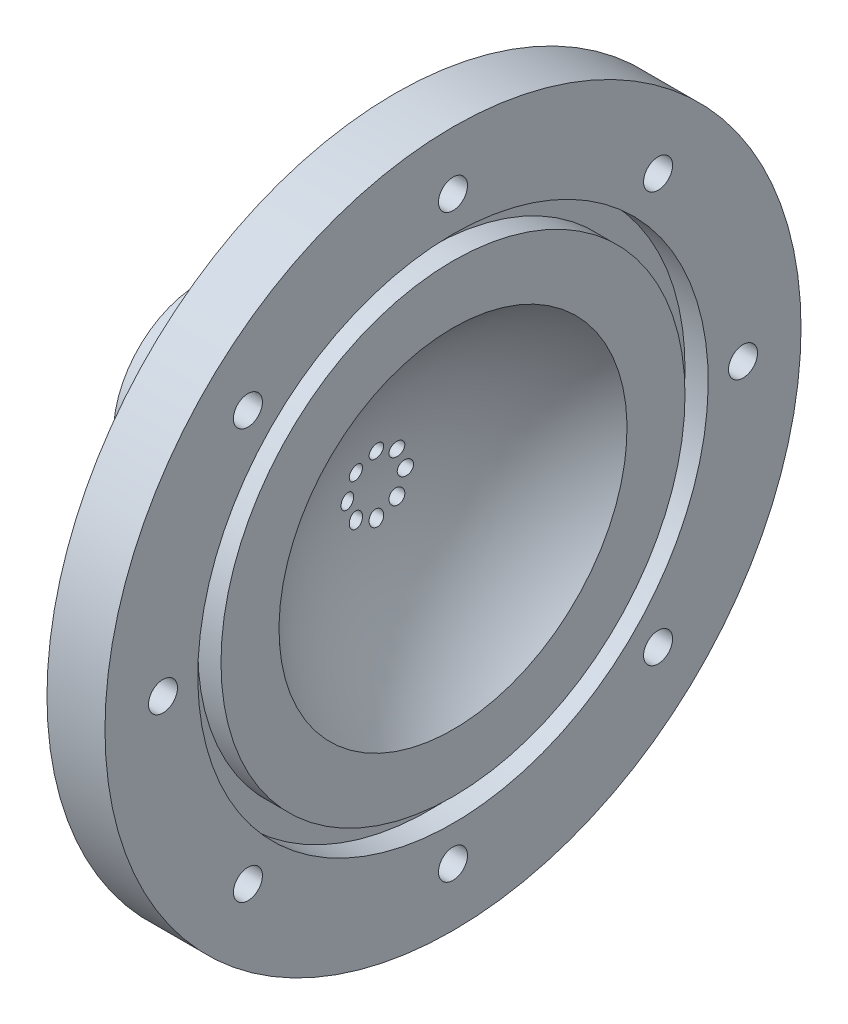
SolidWorks part; units mm, degrees
ref_plane "Front Plane" through (0, 0, 0) normal (0, 0, 1) x (1, 0, 0)
ref_plane "Top Plane" through (0, 0, 0) normal (0, 1, 0) x (1, 0, 0)
ref_plane "Right Plane" through (0, 0, 0) normal (1, 0, 0) x (0, 0, -1)
ref_axis "Axis1" through (-98.515, 0, 0) along (1, 0, 0)
sketch "Sketch1" plane through (0, 0, 0) normal (0, 0, 1) x (1, 0, 0)
  line L0 (0, 38.1) -> (0, 27.94)
  line L1 (-8.5995, 0) -> (-27.6495, 0)
  line L2 (-27.6495, 0) -> (-27.6495, 9.525)
  line L3 (-27.6495, 9.525) -> (-13.487, 9.525)
  line L4 (-6.35, 21.7282) -> (-6.35, 38.1)
  line L5 (-6.35, 38.1) -> (0, 38.1)
  line L6 (0, 19.05) -> (0, 25.4)
  line L7 (0, 25.4) -> (-2.54, 25.4)
  line L8 (-2.54, 25.4) -> (-2.54, 27.94)
  line L9 (-2.54, 27.94) -> (0, 27.94)
  line L10 (-98.515, 0) -> (79.465, 0) construction
  arc A0 (0, 19.05) -> (-8.5995, 0) centre (16.8005, 0) ccw
  arc A1 (-6.35, 21.7282) -> (-13.487, 9.525) centre (16.8005, 0) ccw
  point P1 (-6.35, 19.3161)
  point P6 (-6.35, 19.8543)
  point P8 (-1.27, 25.4)
  point P15 (-6.35, 18.6582)
  point P19 (-10.5795, 12.7433)
  dimension "D2" = 25.4
  dimension "D8" = 31.75
  dimension "D3" = 6.35
  dimension "D4" = 9.525
  dimension "D5" = 2.54
  dimension "D6" = 2.54
  dimension "D7" = 25.4
  dimension "D9" = 19.05
  dimension "D10" = 19.05
  dimension "D11" = 38.1
revolve "Revolve1" add sketch "Sketch1" angle 360 about L1
hole_wizard "1/4 NPT Tapped Hole1" positions "Sketch4" profile "Sketch5" size "1/4" standard "ANSI Inch"
sketch "Sketch4" plane through (-27.6495, 0, 0) normal (-1, 0, 0) x (0, 0, 1)
  point P0 (0, 0)
cosmetic thread "Hole Thread1" parameters "D1"=9.906, "D2"=13.7086
sketch "Sketch5" plane through (-27.6495, 0, 0) normal (0, 1, 0) x (0, 0, 1)
  line L0 (0, 0) -> (0, 16.0423)
  line L1 (5.5626, 12.7) -> (0, 16.0423)
  line L2 (-5.5626, 12.7) -> (0, 16.0423) construction
  line L3 (5.5626, 12.7) -> (5.5626, 9.906)
  line L4 (5.5626, 9.906) -> (5.9437, 9.906)
  line L5 (5.9437, 9.906) -> (6.2403, 0)
  line L6 (-5.9437, 9.906) -> (-6.2403, 0) construction
  line L7 (6.2403, 0) -> (0, 0)
  line L8 (0, -6.35) -> (0, 107.95) construction
  line L11 (-5.5626, 9.906) -> (-5.9437, 9.906) construction
  dimension "Tap Drill Dia." = 11.1252
  dimension "Tap Drill Depth" = 12.7
  dimension "Thread Dia." = 12.4806
  dimension "Thread Angle" = 3.43
  dimension "Thread Depth" = 9.906
  dimension "Drill Angle" = 118
hole_wizard "1/16 (0.0625) Diameter Hole1" positions "Sketch6" profile "Sketch7" hole size "1/16" standard "ANSI Inch" end condition through all
sketch "Sketch6" plane through (0, 0, 0) normal (1, 0, 0) x (0, 0, -1)
  point P0 (0, 3.175)
  dimension "D1" = 3.175
sketch "Sketch7" plane through (0, 3.175, 0) normal (0, 1, 0) x (0, 0, -1)
  line L0 (0, 0) -> (0, 27.6495)
  line L1 (0, 27.6495) -> (0.7937, 27.6495)
  line L2 (0.7937, 27.6495) -> (0.7937, 0)
  line L5 (0.7937, 0) -> (0, 0)
  line L11 (0, -6.35) -> (0, 107.95) construction
  dimension "Thru Hole Dia." = 1.5875
  dimension "Thru Hole Depth" = 27.6495
pattern_circular "CirPattern2" count 8 over 360 about axis through (-98.515, 0, 0) along (1, 0, 0) of "1/16 (0.0625) Diameter Hole1"
hole_wizard "1/8 (0.125) Diameter Hole1" positions "Sketch2" profile "Sketch3" hole size "1/8" standard "ANSI Inch" end condition through all
sketch "Sketch2" plane through (0, 0, 0) normal (1, 0, 0) x (0, 0, -1)
  point P0 (0, 31.75)
  dimension "D1" = 31.75
sketch "Sketch3" plane through (0, 31.75, 0) normal (0, 1, 0) x (0, 0, -1)
  line L0 (0, 0) -> (0, 27.6495)
  line L1 (0, 27.6495) -> (1.5875, 27.6495)
  line L2 (1.5875, 27.6495) -> (1.5875, 0)
  line L5 (1.5875, 0) -> (0, 0)
  line L11 (0, -6.35) -> (0, 107.95) construction
  dimension "Thru Hole Dia." = 3.175
  dimension "Thru Hole Depth" = 27.6495
pattern_circular "CirPattern1" count 8 over 360 about axis through (-98.515, 0, 0) along (1, 0, 0) of "1/8 (0.125) Diameter Hole1"
